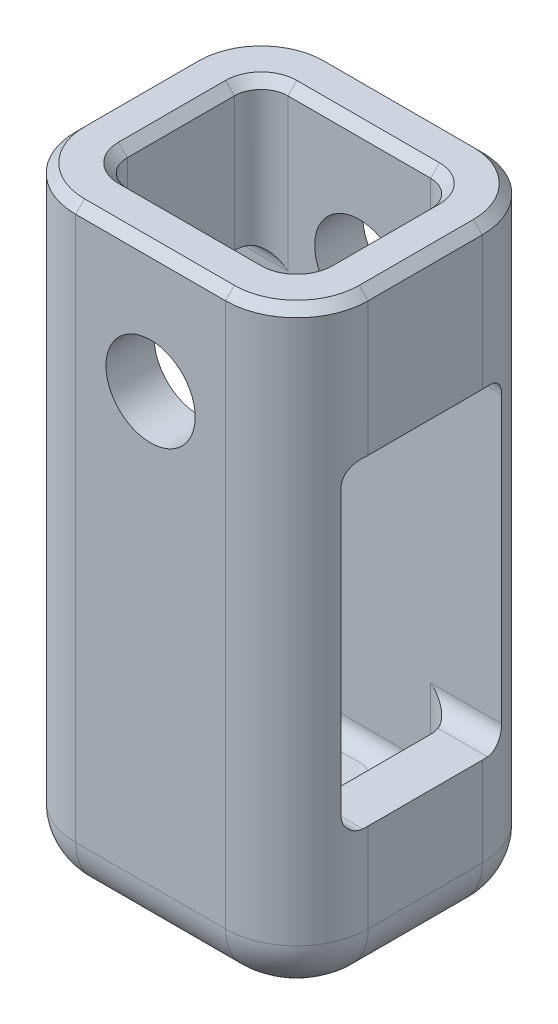
SolidWorks part; units mm, degrees
other "Markup1"
sketch "Sketch6" plane through (-4, 8, -3.5) normal (-0.1216, 0.9914, -0.0475) x (-0.0131, 0.0463, 0.9988)
material "7075 T651 protolabs"
ref_plane "Front Plane" through (0, 0, 0) normal (0, 0, 1) x (1, 0, 0)
ref_plane "Top Plane" through (0, 0, 0) normal (0, 1, 0) x (1, 0, 0)
ref_plane "Right Plane" through (0, 0, 0) normal (1, 0, 0) x (0, 0, -1)
sketch "Sketch1" plane through (0, 0, 0) normal (0, 1, 0) x (1, 0, 0)
  line L1 (-4.1, -3.6) -> (4.1, -3.6)
  line L2 (-4.1, -3.6) -> (-4.1, 3.6)
  line L3 (-4.1, 3.6) -> (4.1, 3.6)
  line L4 (4.1, -3.6) -> (4.1, 3.6)
  line L5 (-4.1, -3.6) -> (4.1, 3.6) construction
  line L6 (-4.1, 3.6) -> (4.1, -3.6) construction
  point P0 (0, 0)
  dimension "D1" = 7.2
  dimension "D2" = 8.2
extrude "Boss-Extrude1" add sketch "Sketch1" along normal mid plane 17
sketch "Sketch2" plane through (0, 8.5, 0) normal (0, 1, 0) x (1, 0, 0)
  line L0 (-2.75, 2) -> (-2.75, 2.25)
  line L3 (2.5, -2.25) -> (-2.5, -2.25)
  line L4 (2.5, -2.25) -> (2.5, 2.25)
  line L5 (2.5, 2.25) -> (-2.5, 2.25)
  line L6 (-2.5, -2.25) -> (-2.5, 2.25)
  line L7 (2.5, -2.25) -> (-2.5, 2.25) construction
  line L8 (2.5, 2.25) -> (-2.5, -2.25) construction
  line L9 (-2.75, -2) -> (2.75, -2)
  line L10 (-2.75, -2) -> (-2.75, 2)
  line L11 (-2.75, 2) -> (2.75, 2)
  line L12 (2.75, -2) -> (2.75, 2)
  line L13 (-2.75, -2) -> (2.75, 2) construction
  line L14 (-2.75, 2) -> (2.75, -2) construction
  line L15 (-2.75, 2.25) -> (-2.5, 2.25)
  line L16 (2.5, 2.25) -> (2.75, 2.25)
  line L17 (2.75, 2.25) -> (2.75, 2)
  line L18 (2.75, -2) -> (2.75, -2.25)
  line L19 (2.75, -2.25) -> (2.5, -2.25)
  line L20 (-2.5, -2.25) -> (-2.75, -2.25)
  line L21 (-2.75, -2.25) -> (-2.75, -2)
  point P0 (0, 0)
  point P2 (0, 0)
  dimension "D1" = 5
  dimension "D2" = 4.5
  dimension "D3" = 4
  dimension "D4" = 5.5
extrude "chain" cut sketch "Sketch2" against normal offset from surface (15 mm away) 2 contours L15 L0 L11 L6 | L11 L10 L9 L6 | L6 L11 L4 L5 | L11 L6 L9 L4 | L17 L16 L4 L11 | L9 L12 L11 L4 | L19 L18 L9 L4 | L9 L6 L3 L4 | L21 L20 L6 L9 up to face at (0, -8.5, 0)
sketch "Sketch13" [suppressed] plane through (0, 8.5, 0) normal (0, 1, 0) x (1, 0, 0)
  line L1 (-2.75, -2.5) -> (2.75, -2.5)
  line L2 (-2.75, -2.5) -> (-2.75, 2.5)
  line L3 (-2.75, 2.5) -> (2.75, 2.5)
  line L4 (2.75, -2.5) -> (2.75, 2.5)
  line L5 (-2.75, -2.5) -> (2.75, 2.5) construction
  line L6 (-2.75, 2.5) -> (2.75, -2.5) construction
  point P0 (0, 0)
  dimension "D1" = 5
  dimension "D2" = 5.5
sketch "Sketch3" plane through (0, 0, 0) normal (0, 0, 1) x (1, 0, 0)
  line L0 (4.1, 8.5) -> (-4.1, 8.5) construction
  line L2 (-4.1, -8.5) -> (4.1, -8.5) construction
  circle A0 centre (0, 5) radius 1.25
  dimension "D1" = 2.5
  dimension "D2" = 13.5
  dimension "D3" = 3.5
extrude "2.5 mm dowel" cut sketch "Sketch3" against normal through all both and the other way through all
sketch "Sketch10" plane through (0, 0, 0) normal (0, 0, 1) x (1, 0, 0)
  line L0 (-4.1, 8.5) -> (4.1, 8.5) construction
  line L1 (-4.1, -8.5) -> (4.1, -8.5) construction
  circle A0 centre (0, 5) radius 0.9922
  dimension "D1" = 3.5
  dimension "D3" = 1.9844
  dimension "D2" = 13.5
extrude "5/64 in dowel" [suppressed] cut sketch "Sketch10" against normal through all both and the other way through all
sketch "Sketch11" plane through (0, 0, 0) normal (0, 0, 1) x (1, 0, 0)
  line L0 (-4.1, 8.5) -> (4.1, 8.5) construction
  line L2 (-4.1, -8.5) -> (4.1, -8.5) construction
  circle A0 centre (0, 5) radius 0.7938
  dimension "D1" = 3.5
  dimension "D3" = 1.5875
  dimension "D2" = 13.5
extrude "1/16 in dowel" [suppressed] cut sketch "Sketch11" against normal through all both and the other way through all
sketch "Sketch4" plane through (0, 0, 0) normal (0, 1, 0) x (1, 0, 0)
  circle A0 centre (0, 0) radius 0.9
  dimension "D1" = 1.8
extrude "steel cable channel" cut sketch "Sketch4" against normal through all
sketch "Sketch12" [suppressed] plane through (0, -8.5, 0) normal (0, -1, 0) x (1, 0, 0)
  circle A0 centre (0, 0) radius 1.2
  dimension "D1" = 2.4
extrude "3/32 cable channel" [suppressed] cut sketch "Sketch12" against normal up to surface (2 mm away) contours A0
sketch "Sketch7" plane through (0, 0, 0) normal (-1, 0, 0) x (0, 0, 1)
  line L0 (-3.6, 8.5) -> (3.6, 8.5) construction
  line L1 (-2.25, 4.5) -> (2.25, 4.5)
  line L2 (-2.25, 4.5) -> (-2.25, -4.5)
  line L3 (-2.25, -4.5) -> (2.25, -4.5)
  line L4 (2.25, 4.5) -> (2.25, -4.5)
  line L6 (-3.6, -8.5) -> (3.6, -8.5) construction
  point P6 (0, 4.5)
  dimension "D1" = 4
  dimension "D2" = 4
  dimension "D3" = 4.5
extrude "crimp window" cut sketch "Sketch7" against normal through all both and the other way through all
fillet "Fillet6" radius 0.75 6 edges at (-2.75, 6.5, -2.25) (-2.75, 6.5, 2.25) (2.75, 6.5, 2.25) (2.75, -5.5, 2.25) (2.75, -5.5, -2.25) (2.75, 6.5, -2.25)
fillet "Fillet7" radius 0.5 8 edges at (2.75, -6.5, 0) (2.5303, -6.5, -2.0303) (2.5303, -6.5, 2.0303) (-2.5303, -6.5, 2.0303) (-2.5303, -6.5, -2.0303) (0, -6.5, -2.25) (0, -6.5, 2.25) (-2.75, -6.5, 0)
fillet "Fillet9" radius 0.5 8 edges at (3.05, 4.5, 2.25) (3.05, 4.5, -2.25) (3.05, -4.5, 2.25) (3.05, -4.5, -2.25) (-3.05, 4.5, 2.25) (-3.05, 4.5, -2.25) (-3.05, -4.5, -2.25) (-3.05, -4.5, 2.25)
fillet "Fillet3" radius 2 4 edges at (-4.1, 0, -3.6) (-4.1, 0, 3.6) (4.1, 0, -3.6) (4.1, 0, 3.6)
fillet "Fillet5" radius 1.5 8 edges at (3.5142, -8.5, 3.0142) (0, -8.5, 3.6) (-3.5142, -8.5, 3.0142) (-4.1, -8.5, 0) (-3.5142, -8.5, -3.0142) (0, -8.5, -3.6) (3.5142, -8.5, -3.0142) (4.1, -8.5, 0)
chamfer "Chamfer1" distance 0.25 angle 45 16 edges at (0, 8.5, 2.25) (0, 8.5, -2.25) (0, 8.5, 3.6) (3.5142, 8.5, 3.0142) (-3.5142, 8.5, 3.0142) (4.1, 8.5, 0) (-4.1, 8.5, 0) (3.5142, 8.5, -3.0142) (-3.5142, 8.5, -3.0142) (0, 8.5, -3.6) (-2.75, 8.5, 0) (2.75, 8.5, 0) (-2.5303, 8.5, 2.0303) (2.5303, 8.5, 2.0303) (-2.5303, 8.5, -2.0303) (2.5303, 8.5, -2.0303)
sketch "Sketch5" plane through (0, -6.5, 0) normal (0, 1, 0) x (1, 0, 0)
  circle A0 centre (0, 0) radius 1.9
  circle A1 centre (0, 0) radius 0.9 construction
  circle A2 centre (0, 0) radius 0.9
  dimension "D1" = 3.8
extrude "Boss-Extrude2" add sketch "Sketch5" along normal blind 0.005
